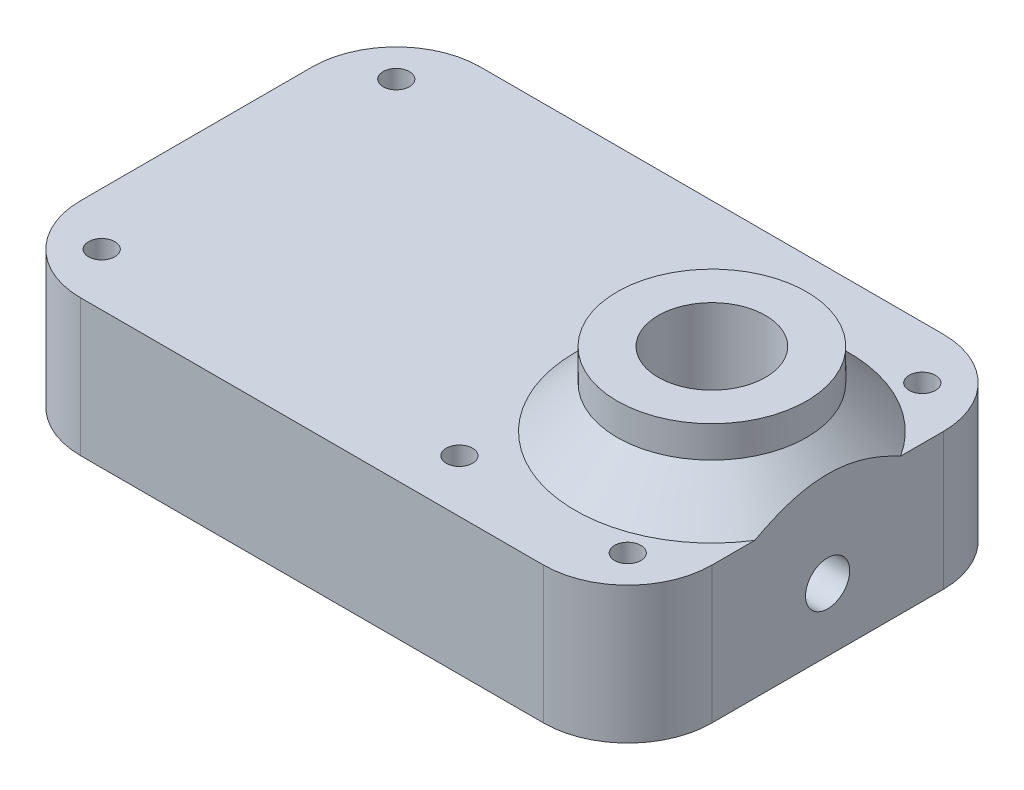
SolidWorks part; units mm, degrees
material "Aluminum 101"
ref_plane "Front Plane" through (0, 0, 0) normal (0, 0, 1) x (1, 0, 0)
ref_plane "Top Plane" through (0, 0, 0) normal (0, 1, 0) x (1, 0, 0)
ref_plane "Right Plane" through (0, 0, 0) normal (1, 0, 0) x (0, 0, -1)
sketch "Sketch1" plane through (0, 0, 0) normal (0, 1, 0) x (1, 0, 0)
  line L1 (-49, 19) -> (11, 19)
  line L2 (-49, 19) -> (-49, -19)
  line L3 (-49, -19) -> (11, -19)
  line L4 (11, 19) -> (11, -19)
  circle A1 centre (0, 0) radius 9
  point P8 (11, 0)
  dimension "D2" = 18
  dimension "D3" = 38
  dimension "D4" = 60
  dimension "D1" = 11
extrude "Base" add sketch "Sketch1" along normal blind 13 contours L4 A1 L1 L2 L3 | A1 region at (-21.387, 0, 0) region at (0, 0, 0)
fillet "AddALittleBeauty" radius 8 4 edges at (-49, 6.5, 19) (-49, 6.5, -19) (11, 6.5, -19) (11, 6.5, 19)
extrude "RodHolder" add sketch "Sketch1<3>" along normal blind 20 contours A1 region at (0, 0, 0)
sketch "Sketch1<3>" plane through (0, 0, 0) normal (0, 1, 0) x (1, 0, 0) same geometry as "Sketch1"
hole_wizard "M5x0.8 Tapped Hole for fixing rod" positions "Sketch3" profile "Sketch4" tap size "M5x0.8" standard "ANSI Metric"
sketch "Sketch3" plane through (11, 0, 0) normal (1, 0, 0) x (0, 0, -1)
  line L0 (11, 0) -> (-11, 0) construction
  point P0 (0, 6)
  dimension "D1" = 6
cosmetic thread "Hole Thread1" parameters "D1"=6.3524, "D2"=5
sketch "Sketch4" plane through (11, 6, 0) normal (0, 1, 0) x (0, 0, -1)
  line L0 (0, 0) -> (0, 11.6618)
  line L1 (0, 11.6618) -> (2.1, 10.4)
  line L2 (2.1, 10.4) -> (2.1, 0)
  line L5 (2.1, 0) -> (0, 0)
  line L10 (0, 11.6618) -> (-2.1, 10.4) construction
  line L11 (0, -6.35) -> (0, 107.95) construction
  dimension "Tap Drill Dia." = 4.2
  dimension "Tap Drill Depth" = 10.4
  dimension "Drill Angle" = 118
chamfer "Chamfer1" distance 4 angle 45 1 edges at (0, 13, 9)
hole_wizard "Ø10.2 (10.2) Rod Hole" positions "Sketch5" profile "Sketch6" hole size "Ø10.2" standard "ANSI Metric" end condition through all
sketch "Sketch5" plane through (0, 20, 0) normal (0, 1, 0) x (1, 0, 0)
  point P0 (0, 0)
sketch "Sketch6" plane through (0, 20, 0) normal (1, 0, 0) x (0, 0, 1)
  line L0 (0, 0) -> (0, 20)
  line L1 (0, 20) -> (5.1, 20)
  line L2 (5.1, 20) -> (5.1, 0)
  line L5 (5.1, 0) -> (0, 0)
  line L11 (0, -6.35) -> (0, 107.95) construction
  dimension "Thru Hole Dia." = 10.2
  dimension "Thru Hole Depth" = 20
hole_wizard "M3x0.5 Tapped Hole1" positions "Location" profile "Hole" tap size "M3x0.5" standard "ANSI Metric" end condition through all
sketch "Location" plane through (0, 0, 0) normal (0, -1, 0) x (-1, 0, 0)
  line L0 (41, 19) -> (-3, 19) construction
  line L2 (49, 11) -> (49, -11) construction
  line L4 (19, 18.3865) -> (19, -17.1189) construction
  line L5 (49, 0) -> (41.0253, 0) construction
  point P0 (-6, 14)
  point P3 (-6, -14)
  point P6 (44, -14)
  point P9 (44, 14)
  point P27 (10, 14)
  point P29 (10, -14)
  point P39 (19, 19)
  point P43 (0, 0)
  point P44 (0, 0)
  point P45 (0, 0)
  point P46 (0, 0)
  point P47 (14.6973, -12.5)
  dimension "D1" = 28
  dimension "D3" = 25
  dimension "D2" = 25
  dimension "D4" = 16
sketch "Hole" plane through (6, 0, -14) normal (1, 0, 0) x (0, 0, -1)
  line L0 (0, 0) -> (0, 20)
  line L1 (0, 20) -> (1.25, 20)
  line L2 (1.25, 20) -> (1.25, 0.275)
  line L3 (1.25, 0.275) -> (1.525, 0)
  line L5 (1.525, 0) -> (0, 0)
  line L6 (-1.25, 0.275) -> (-1.525, 0) construction
  line L11 (0, -6.35) -> (0, 107.95) construction
  dimension "Thru Tap Drill Dia." = 2.5
  dimension "Thru Tap Drill Depth" = 20
  dimension "Near C'Sink Dia." = 3.05
  dimension "Near C'Sink Angle" = 90
cosmetic thread "Hole Thread2" parameters "D2"=3
cosmetic thread "Hole Thread3" parameters "D2"=3
cosmetic thread "Hole Thread4" parameters "D2"=3
cosmetic thread "Hole Thread5" parameters "D2"=3
cosmetic thread "Hole Thread6" parameters "D2"=3
cosmetic thread "Hole Thread7" parameters "D2"=3
sketch "Sketch9" plane through (0, 0, 0) normal (0, -1, 0) x (1, 0, 0)
  line L1 (-49, -11) -> (-49, 11) construction
  line L2 (-13.5, -13.5) -> (-40.5, -13.5)
  line L3 (-13.5, -13.5) -> (-13.5, 13.5)
  line L4 (-13.5, 13.5) -> (-40.5, 13.5)
  line L5 (-40.5, -13.5) -> (-40.5, 13.5)
  line L6 (-13.5, -13.5) -> (-40.5, 13.5) construction
  line L7 (-13.5, 13.5) -> (-40.5, -13.5) construction
  point P2 (-27, 0)
  dimension "D1" = 22
  dimension "D2" = 27
  dimension "D3" = 27
extrude "Cut-Extrude1" cut sketch "Sketch9" against normal blind 9
fillet "Fillet1" radius 2 8 edges at (-40.5, 4.5, -13.5) (-40.5, 4.5, 13.5) (-13.5, 4.5, 13.5) (-13.5, 4.5, -13.5) (-27, 9, 13.5) (-13.5, 9, 0) (-27, 9, -13.5) (-40.5, 9, 0)
equation "\"D2@Sketch1\"=10.00mm+8"
equation "\"D3@Sketch9\"=\"D2@Sketch9\""
equation "\"width\"= \"D3@Sketch1\""
equation "\"length\"= \"D4@Sketch1\""
equation "\"D1@Location\" = \"width\" - 10"
equation "\"D3@Location\"=(\"length\"-10)/2"
equation "\"D2@Location\"=(\"length\"-10)/2"
